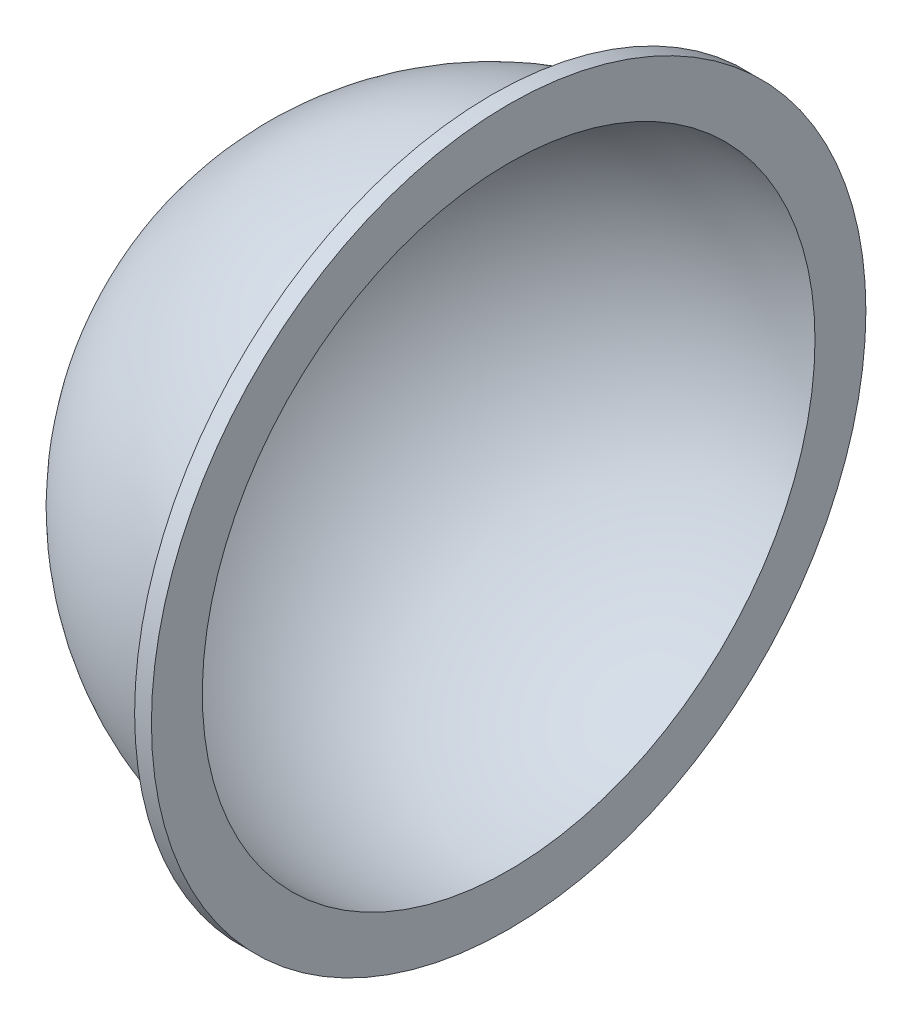
SolidWorks part; units mm, degrees
ref_plane "Front Plane" through (0, 0, 0) normal (0, 0, 1) x (1, 0, 0)
ref_plane "Top Plane" through (0, 0, 0) normal (0, 1, 0) x (1, 0, 0)
ref_plane "Right Plane" through (0, 0, 0) normal (1, 0, 0) x (0, 0, -1)
sketch "Sketch1" plane through (0, 0, 0) normal (0, 0, 1) x (1, 0, 0)
  line L0 (0, 36.5) -> (0, 57.3704)
  line L1 (0, 0) -> (-57.2513, 0)
  line L2 (0, 0) -> (2, 0)
  line L3 (2, 36.4452) -> (2, 57.3704)
  line L4 (2, -2) -> (-57.2513, -2) construction
  line L5 (2, -2) -> (2, 57.3704) construction
  line L6 (0, 42.5) -> (2, 42.5)
  line L7 (0, 0) -> (0, 57.3704) construction
  arc A0 (2, 37.4466) -> (-37.5, 0) centre (0, 0) ccw
  arc A1 (2, 36.4452) -> (-36.5, 0) centre (0, 0) ccw
  dimension "D1" = 2
  dimension "D2" = 42.5
  dimension "D3" = 75
  dimension "D4" = 73
revolve "Revolve1" add sketch "Sketch1" angle 360 about L1 region at (-26.1844, 26.1844, 0) region at (1.0002, 36.982, 0) region at (1.0018, 39.9911, 0)
scale "Scale1" bodies to scale 101 scale about origin uniform scaling yes scale factor 0.8
